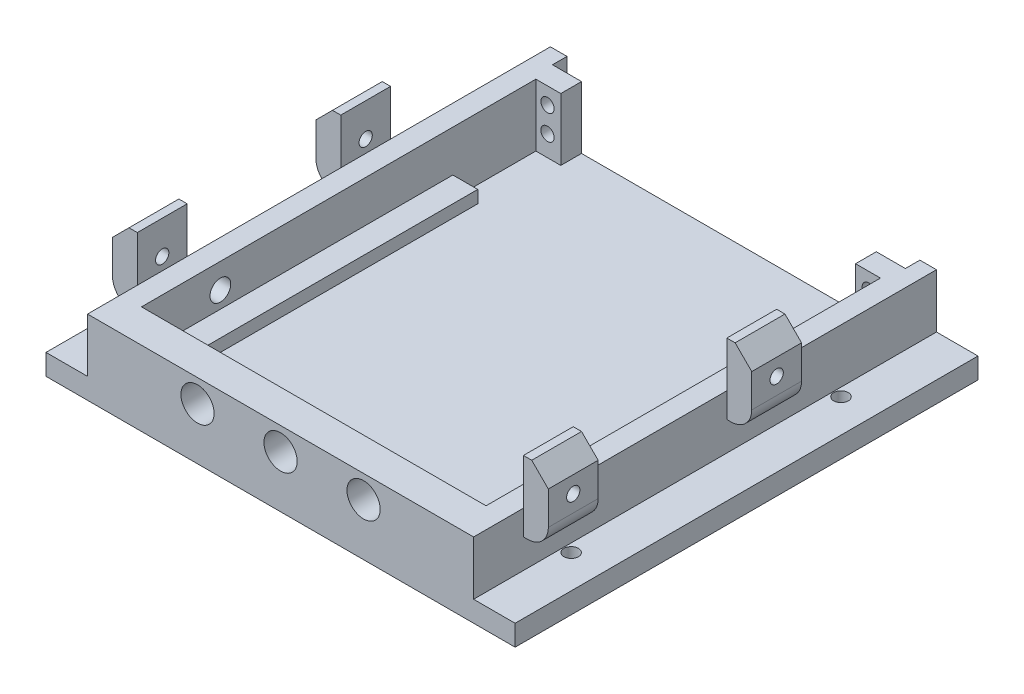
SolidWorks part; units mm, degrees
ref_plane "Alzado" through (0, 0, 0) normal (0, 0, 1) x (1, 0, 0)
ref_plane "Planta" through (0, 0, 0) normal (0, 1, 0) x (1, 0, 0)
ref_plane "Vista lateral" through (0, 0, 0) normal (1, 0, 0) x (0, 0, -1)
sketch "Croquis1" plane through (0, 0, 0) normal (0, 1, 0) x (1, 0, 0)
  line L1 (-46.5, 54) -> (46.5, 54)
  line L2 (-46.5, 54) -> (-46.5, -54)
  line L3 (-46.5, -54) -> (46.5, -54)
  line L4 (46.5, 54) -> (46.5, -54)
  line L5 (-46.5, 54) -> (46.5, -54) construction
  line L6 (-46.5, -54) -> (46.5, 54) construction
  point P0 (0, 0)
  dimension "D1" = 108
  dimension "D2" = 93
extrude "Saliente-Extruir1" add sketch "Croquis1" along normal blind 3
sketch "Croquis2" plane through (0, 3, 0) normal (0, 1, 0) x (1, 0, 0)
  line L1 (-46.5, 54) -> (-41.5, 54)
  line L2 (-46.5, 54) -> (-46.5, -54)
  line L4 (-41.5, 54) -> (-41.5, -46)
  line L5 (46.5, 54) -> (-46.5, 54) construction
  line L7 (46.5, -54) -> (46.5, 54)
  line L8 (46.5, 54) -> (41.5, 54)
  line L9 (41.5, -46) -> (41.5, 54)
  line L10 (-46.5, -54) -> (46.5, -54)
  line L12 (-41.5, -46) -> (41.5, -46)
  dimension "D1" = 5
  dimension "D2" = 5
  dimension "D3" = 100
  dimension "D4" = 100
extrude "Saliente-Extruir2" add sketch "Croquis2" along normal blind 15
ref_plane "Plano1" through (0, 0, -48) normal (0, 0, -1) x (-1, 0, 0)
sketch "Croquis10" plane through (46.5, 0, 0) normal (1, 0, 0) x (0, 0, -1)
  line L0 (13, 29) -> (13, 12) construction
  line L5 (-33, 18) -> (10, 18) construction
  line L10 (51.15, 0) -> (-51.15, 0) construction
  line L15 (10, 12) -> (19, 12)
  line L16 (10, 12) -> (10, 29)
  line L17 (10, 29) -> (19, 29)
  line L18 (19, 12) -> (19, 29)
  line L19 (-36, 12) -> (-30, 12)
  line L20 (13, 12) -> (7, 12)
  line L22 (13, 29) -> (7, 29)
  line L23 (7, 12) -> (7, 29)
  line L24 (-33, 12) -> (-42, 12)
  line L25 (-11.5, 11.4546) -> (-11.5, 24.5454)
  line L26 (54, 18) -> (54, 0) construction
  line L27 (-54, 18) -> (-54, 0) construction
  line L28 (-54, 0) -> (54, 0) construction
  line L29 (-42, 12) -> (-42, 29)
  line L30 (-36, 29) -> (-30, 29)
  line L31 (-33, 29) -> (-42, 29)
  line L32 (-30, 12) -> (-30, 29)
  circle A1 centre (13, 21) radius 1.6
  circle A2 centre (-36, 21) radius 1.6
  point P25 (-11.5, 18)
  line M7 (54, 18) -> (-54, 18)
  dimension "D10" = 3.2
  dimension "D8" = 9
  dimension "D4" = 8
  dimension "D2" = 12
  dimension "D3" = 35
  dimension "D5" = 12
  dimension "D6" = 21
  dimension "D7" = 18
  dimension "D14" = 3
  dimension "D15" = 6
extrude "Saliente-Extruir4" add sketch "Croquis10" along normal blind 6 contours L18 L17 L16 A1 M7 | L15 L18 L16 M7 | L23 L20 L16 M7 | L23 L16 L22 M7 | L32 L30 L31 L29 A2 M7 | L19 L32 L29 L24 M7 region at (46.5, 15, -14.5) region at (46.5, 15, -8.5) region at (46.5, 15, 36) region at (46.5, 23.6622, 36) region at (46.5, 23.5, -8.5) region at (46.5, 23.7211, -14.6326)
fillet "Redondeo1" radius 5 2 edges at (52.5, 12, -13) (52.5, 12, 36)
mirror "Simetría1" about plane through (0, 0, 0) normal (1, 0, 0) of "Saliente-Extruir4", "Redondeo1"
sketch "Croquis12" plane through (-41.5, 0, 0) normal (1, 0, 0) x (0, 0, -1)
  line L0 (-46, 18) -> (54, 18) construction
  line L1 (49, 18) -> (54, 18)
  line L2 (49, 18) -> (49, 3)
  line L3 (49, 3) -> (54, 3)
  line L4 (54, 18) -> (54, 3)
  dimension "D1" = 5
extrude "Saliente-Extruir5" add sketch "Croquis12" along normal blind 6
mirror "Simetría2" about plane through (0, 0, 0) normal (1, 0, 0) of "Saliente-Extruir5"
sketch "Croquis13" plane through (0, 0, 54) normal (0, 0, 1) x (1, 0, 0)
  line L0 (-46.5, 0) -> (46.5, 0) construction
  line L2 (0, 12.5) -> (20, 12.5) construction
  line L3 (0, 12.5) -> (-20, 12.5) construction
  line L4 (0, 0) -> (0, 12.5) construction
  circle A0 centre (-20, 12.5) radius 4
  circle A1 centre (0, 12.5) radius 4
  circle A2 centre (20, 12.5) radius 4
  dimension "D1" = 8
  dimension "D2" = 8
  dimension "D3" = 8
  dimension "D4" = 12.5
  dimension "D5" = 20
  dimension "D6" = 20
extrude "Cortar-Extruir1" cut sketch "Croquis13" against normal up to next
sketch "Croquis14" plane through (0, 0, -54) normal (0, 0, -1) x (-1, 0, 0)
  line L0 (38.7, 14) -> (38.7, 8) construction
  line L2 (35.5, 18) -> (46.5, 18) construction
  line L3 (35.5, 3) -> (35.5, 18) construction
  circle A0 centre (38.7, 14) radius 1.6
  circle A1 centre (38.7, 8) radius 1.6
  dimension "D1" = 3.2
  dimension "D2" = 3.2
  dimension "D3" = 6
  dimension "D4" = 4
  dimension "D5" = 3.2
extrude "Cortar-Extruir2" cut sketch "Croquis14" against normal up to next
mirror "Simetría3" about plane through (0, 0, 0) normal (1, 0, 0) of "Cortar-Extruir2"
sketch "Croquis15" plane through (0, 0, -54) normal (0, 0, -1) x (-1, 0, 0)
  line L0 (-38.7, 14) -> (38.7, 14) construction
sketch "Croquis16" plane through (-46.5, 0, 0) normal (-1, 0, 0) x (0, 0, 1)
  line L0 (0, 0) -> (0, 12) construction
  line L1 (-54, 0) -> (54, 0) construction
  line L3 (0, 12) -> (27, 12) construction
  circle A0 centre (27, 12) radius 2.5
  dimension "D1" = 5
  dimension "D2" = 12
  dimension "D3" = 27
extrude "Cortar-Extruir3" cut sketch "Croquis16" against normal blind 93
sketch "Croquis17" plane through (0, 0, 0) normal (0, 1, 0) x (1, 0, 0)
  line L6 (46.5, 54) -> (42.5, 54)
  line L7 (46.5, 54) -> (46.5, 57.5)
  line L8 (46.5, 57.5) -> (42.5, 57.5)
  line L9 (42.5, 54) -> (42.5, 57.5)
  dimension "D1" = 3.5
  dimension "D2" = 4
extrude "Saliente-Extruir6" add sketch "Croquis17" along normal up to surface (18 mm away) up to face at (0, 18, -6)
mirror "Simetría4" about plane through (0, 0, 0) normal (1, 0, 0) of "Saliente-Extruir6"
chamfer "Chaflán2" distance 4 angle 45 4 edges at (52.5, 29, -13) (52.5, 29, 36) (-52.5, 29, -13) (-52.5, 29, 36)
sketch "Croquis18" plane through (46.5, 0, 0) normal (1, 0, 0) x (0, 0, -1)
  line L5 (57.5, 18) -> (57.5, 0) construction
  line L6 (-54, 0) -> (57.5, 0)
  line L7 (-54, 0) -> (-54, 5)
  line L8 (-54, 5) -> (57.5, 5)
  line L9 (57.5, 0) -> (57.5, 5)
  dimension "D1" = 5
extrude "Saliente-Extruir7" add sketch "Croquis18" along normal blind 10
sketch "Croquis20" plane through (-41.5, 0, 0) normal (1, 0, 0) x (0, 0, -1)
  line L0 (-46, 18) -> (-46, 3) construction
  line L1 (-46, 8) -> (29, 8)
  line L2 (-46, 8) -> (-46, 5)
  line L3 (-46, 5) -> (29, 5)
  line L4 (29, 8) -> (29, 5)
  line L5 (-46, 3) -> (49, 3) construction
  dimension "D1" = 3
  dimension "D2" = 75
  dimension "D3" = 2
extrude "Saliente-Extruir8" add sketch "Croquis20" along normal blind 6
mirror "Simetría9" about plane through (0, 0, 0) normal (1, 0, 0) of "Saliente-Extruir8"
sketch "Croquis21" plane through (46.5, 0, 0) normal (-1, 0, 0) x (0, 0, 1)
  circle A1 centre (36, 21) radius 1.6
sketch "Croquis22" plane through (-46.5, 0, 0) normal (1, 0, 0) x (0, 0, -1)
  circle A0 centre (13, 21) radius 1.6
sketch "Croquis24" plane through (0, 5, 0) normal (0, 1, 0) x (1, 0, 0)
  line L0 (56.5, 57.5) -> (56.5, -54) construction
  line L1 (56.5, 57.5) -> (46.5, 57.5) construction
  circle A0 centre (48.5, 32.5) radius 1.75
  dimension "D1" = 3.5
  dimension "D2" = 8
  dimension "D3" = 25
extrude "Cortar-Extruir4" cut sketch "Croquis24" against normal up to next
mirror "Simetría11" about plane through (0, 0, 0) normal (0, 0, 1) of "Cortar-Extruir4"
mirror "Simetría12" about plane through (0, 0, 0) normal (1, 0, 0) of "Simetría11", "Saliente-Extruir7", "Cortar-Extruir4"
sketch "Croquis28" plane through (0, 0, -54) normal (0, 0, -1) x (-1, 0, 0)
  circle A0 centre (-38.7, 14) radius 1.6
